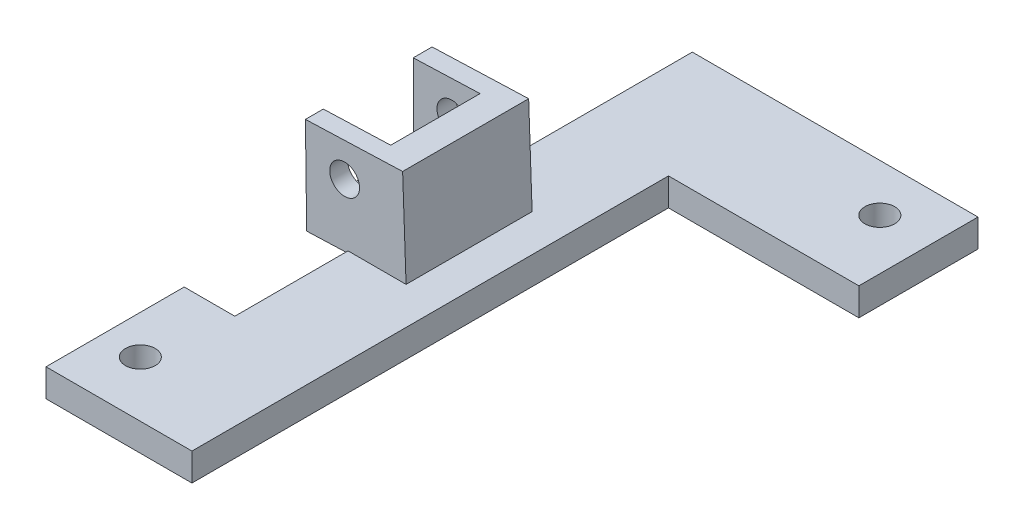
SolidWorks part; units mm, degrees
ref_plane "Front Plane" through (0, 0, 0) normal (0, 0, 1) x (1, 0, 0)
ref_plane "Top Plane" through (0, 0, 0) normal (0, 1, 0) x (1, 0, 0)
ref_plane "Right Plane" through (0, 0, 0) normal (1, 0, 0) x (0, 0, -1)
sketch "Sketch1" plane through (0, 0, 0) normal (0, 0, 1) x (1, 0, 0)
  line L0 (337.3168, 116.8505) -> (338.0523, 96.3659)
  line L1 (330.9022, 116.6201) -> (352.1622, 117.3835) construction
  line L2 (338.0523, 96.3659) -> (359.2436, 97.1267)
  line L3 (359.2436, 97.1267) -> (358.5081, 117.6113)
  line L4 (358.5081, 117.6113) -> (337.3168, 116.8505)
  line L5 (330.7578, 99.9164) -> (346.4865, 100.4811) construction
  line L6 (330.7578, 99.9164) -> (346.4865, 100.4811)
  line L7 (337.9156, 100.1734) -> (346.4865, 100.4811)
  arc A0 (346.4865, 100.4811) -> (352.6762, 103.0671) centre (346.1447, 110) ccw construction
  arc A1 (352.6762, 103.0671) -> (352.1622, 117.3835) centre (346.1447, 110) ccw construction
  arc A2 (346.4865, 100.4811) -> (352.6762, 103.0671) centre (346.1447, 110) ccw
  arc A3 (352.6762, 103.0671) -> (352.1622, 117.3835) centre (346.1447, 110) ccw
  arc A4 (352.1622, 117.3835) -> (352.6762, 103.0671) centre (346.1447, 110) cw
  arc A5 (352.6762, 103.0671) -> (346.4865, 100.4811) centre (346.1447, 110) cw
  dimension "D1" = 6.35
  dimension "D2" = 3.81
extrude "Boss-Extrude2" add sketch "Sketch1" against normal blind 23.0618 contours A3 A2 L6 L0 L2 L3 L4 region at (342.2118, 100.0264, 0)
sketch "Sketch5" plane through (0, 0, -23.0618) normal (0, 0, -1) x (-1, 0, 0)
  line L0 (-352.1622, 117.3835) -> (-337.9156, 116.872)
  line L1 (-337.9156, 116.872) -> (-337.9156, 100.1734)
  line L2 (-337.9156, 100.1734) -> (-346.4865, 100.4811)
  arc A0 (-346.4865, 100.4811) -> (-352.1622, 117.3835) centre (-346.1447, 110) cw
  circle A1 centre (-346.1447, 110) radius 3.175 construction
  circle A2 centre (-346.1447, 110) radius 3.175
  circle A3 centre (-346.1447, 110) radius 3.175
  arc M5 (-346.4865, 100.4811) -> (-352.1622, 117.3835) centre (-346.1447, 110) cw
  line M10 (-337.9156, 100.1734) -> (-346.4865, 100.4811)
extrude "Boss-Extrude3" add sketch "Sketch5" against normal up to surface (4.0118 mm away) contours L1 L0 A2 M5 M10 region at (345.0477, 116.8806, -23.0618)
sketch "Sketch6" plane through (0, 0, 0) normal (0, 0, 1) x (1, 0, 0)
  line L0 (337.7808, 116.8671) -> (338.0523, 96.3659)
  line L1 (330.9022, 116.6201) -> (352.1622, 117.3835) construction
  line L2 (338.0523, 96.3659) -> (359.2436, 97.1267)
  line L3 (359.2436, 97.1267) -> (358.5081, 117.6113)
  line L4 (358.5081, 117.6113) -> (352.1622, 117.3835) construction
  line L5 (359.2436, 97.1267) -> (358.5081, 117.6113) construction
  line L6 (358.5081, 117.6113) -> (337.7808, 116.8671)
  circle A0 centre (346.1447, 110) radius 3.175
extrude "Boss-Extrude5" add sketch "Sketch6" along normal blind 3.81
ref_plane "Plane1" through (0, 97.1267, 0) normal (0, 1, 0) x (1, 0, 0)
sketch "Sketch7" plane through (0, 97.1267, 0) normal (0, 1, 0) x (1, 0, 0)
  line L0 (367.1845, -32.004) -> (367.1845, -57.404)
  line L2 (346.8645, 44.958) -> (346.8645, -27.94)
  line L4 (367.1845, 44.196) -> (367.1845, -32.004)
  line L5 (367.1845, -57.404) -> (336.7045, -57.404)
  line L6 (336.7045, -57.404) -> (336.7045, -27.94)
  line L7 (336.7045, -27.94) -> (346.8645, -27.94)
  line L8 (346.8645, 44.958) -> (346.8645, 69.596)
  line L9 (346.8645, 69.596) -> (407.8245, 69.596)
  line L10 (407.8245, 69.596) -> (407.8245, 44.196)
  line L11 (407.8245, 44.196) -> (367.1845, 44.196)
  circle A0 centre (396.9775, 59.4568) radius 3.175
  circle A1 centre (344.3245, -45.5528) radius 3.175
  circle A2 centre (344.3245, -45.5528) radius 3.175 construction
  dimension "D5" = 25.4
  dimension "D8" = 6.35
  dimension "D9" = 6.35
  dimension "D1" = 30.48
  dimension "D2" = 60.96
  dimension "D3" = 25.4
  dimension "D4" = 76.2
  dimension "D6" = 72.898
  dimension "D7" = 24.638
  dimension "D10" = 127
  dimension "D11" = 20.32
  dimension "D12" = 53.594
  dimension "D13" = 7.62
extrude "Boss-Extrude6" add sketch "Sketch7" against normal up to surface (5.9153 mm away)
sketch "Sketch8" plane through (336.7045, 0, 0) normal (-1, 0, 0) x (0, 0, 1)
  line L1 (57.404, 91.2114) -> (27.94, 91.2114)
  line L2 (57.404, 91.2114) -> (57.404, 97.1267)
  line L3 (57.404, 97.1267) -> (27.94, 97.1267)
  line L4 (27.94, 91.2114) -> (27.94, 97.1267)
extrude "Boss-Extrude7" add sketch "Sketch8" along normal blind 0.635
sketch "Sketch9" plane through (407.8245, 0, 0) normal (1, 0, 0) x (0, 0, -1)
  line L1 (44.196, 91.2114) -> (69.596, 91.2114)
  line L2 (44.196, 91.2114) -> (44.196, 97.1267)
  line L3 (44.196, 97.1267) -> (69.596, 97.1267)
  line L4 (69.596, 91.2114) -> (69.596, 97.1267)
extrude "Cut-Extrude2" cut sketch "Sketch9" against normal blind 0.052
